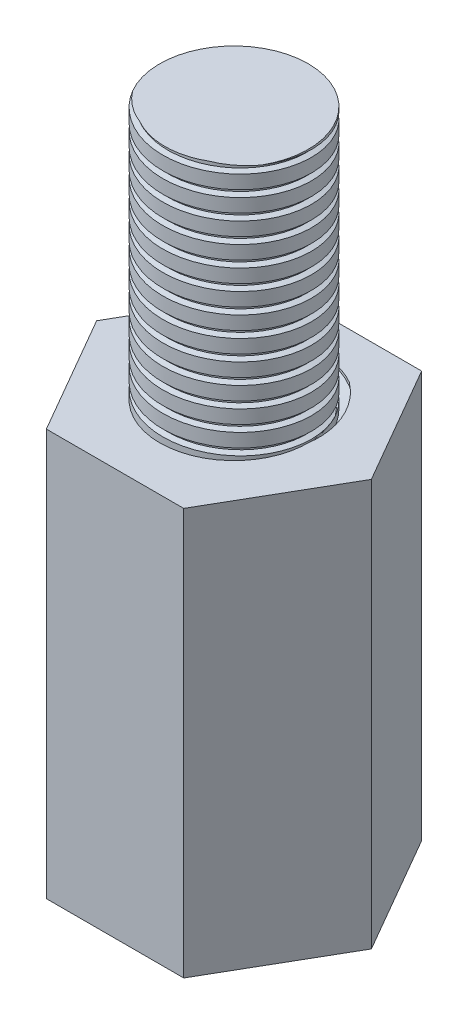
SolidWorks part; units mm, degrees
note: The reader was unsure of these and kept them because the rebuilt part matched: shared geometry of "草图1<3>".
ref_plane "前视基准面" through (0, 0, 0) normal (0, 0, 1) x (1, 0, 0)
ref_plane "上视基准面" through (0, 0, 0) normal (0, 1, 0) x (1, 0, 0)
ref_plane "右视基准面" through (0, 0, 0) normal (1, 0, 0) x (0, 0, -1)
sketch "草图1" plane through (0, 0, 0) normal (0, 1, 0) x (1, 0, 0)
  line L0 (0, 0) -> (0, 4.5761) construction
  line L1 (1.351, -2.34) -> (2.702, 0)
  line L2 (2.702, 0) -> (1.351, 2.34)
  line L3 (1.351, 2.34) -> (-1.351, 2.34)
  line L4 (-1.351, 2.34) -> (-2.702, 0)
  line L5 (-2.702, 0) -> (-1.351, -2.34)
  line L6 (-1.351, -2.34) -> (1.351, -2.34)
  line L7 (0, 4.5761) -> (0, -3.6794) construction
  circle A0 centre (0, 0) radius 2.34 construction
  circle A1 centre (0, 0) radius 1.46
  dimension "D1" = 4.68
  dimension "D2" = 2.92
extrude "凸台-拉伸1" add sketch "草图1" along normal blind 8 contours A1 | L5 L6 L1 L2 L3 L4 A1
extrude "切除-拉伸1" cut sketch "草图1<3>" along normal blind 5 contours A1
sketch "草图1<3>" plane through (0, 0, 0) normal (0, 1, 0) x (1, 0, 0) same geometry as "草图1"
sketch "草图2" plane through (0, 8, 0) normal (0, 1, 0) x (1, 0, 0)
  circle A0 centre (0, 0) radius 1.46
  dimension "D1" = 2.92
extrude "凸台-拉伸2" add sketch "草图2" along normal blind 5 separate body
ref_plane "基准面1" through (0, 0, 0) normal (0, 0, -1) x (-1, 0, 0)
sketch "草图4" plane through (0, 0, 0) normal (0, 0, -1) x (-1, 0, 0)
  line L0 (0, 0) -> (0, 28.5702) construction
  line L1 (-1.56, 8) -> (-1.56, 8.2)
  line L2 (-1.56, 8.2) -> (-1.36, 8.1333)
  line L3 (-1.36, 8.0667) -> (-1.56, 8)
  line L4 (-1.26, 8.1) -> (-2.0659, 8.1) construction
  line L5 (-2.0659, 8.1) -> (-0.8933, 8.1) construction
  line L7 (-1.46, 13) -> (-1.46, 8) construction
  line L8 (-1.36, 8.1333) -> (-1.36, 8.0667)
  line L9 (-1.46, 8) -> (1.46, 8) construction
  point P14 (0, 0)
  point P15 (0, 0)
  dimension "D1" = 0.1
  dimension "D2" = 0.1
  dimension "D3" = 0.1
  dimension "D4" = 0.3
  dimension "D5" = 0.2
  dimension "D6" = 0.1
  dimension "D7" = 0.0667
  dimension "D8" = 0.0667
ref_plane "基准面2" through (0, 8.1, 0) normal (0, 1, 0) x (1, 0, 0)
sketch "草图5" plane through (0, 8.1, 0) normal (0, 1, 0) x (1, 0, 0)
  circle A0 centre (0, 0) radius 1.46
  dimension "D1" = 2.92
curve "螺旋线/涡状线1" pitch 0.4 height 7.5 turns 18.75
sweep "切除-扫描1" cut profiles "草图4" path "螺旋线/涡状线1"
sketch "草图6" plane through (0, 0, 0) normal (0, -1, 0) x (1, 0, 0)
  circle A0 centre (0, 0) radius 1.46
curve "螺旋线/涡状线2" pitch 0.4 height 9.5 turns 23.75
sketch "草图7" plane through (0, 0, 0) normal (0, 0, -1) x (-1, 0, 0)
  line L0 (1.46, 0.2) -> (1.66, 0.1333)
  line L1 (1.66, 0.0667) -> (1.46, 0)
  line L2 (1.46, 0.2) -> (1.46, 0)
  line L3 (1.66, 0.1333) -> (1.66, 0.0667)
  line L8 (1.351, 0) -> (-1.351, 0) construction
  dimension "D1" = 0.2
  dimension "D3" = 1.46
  dimension "D4" = 0.2
sweep "切除-扫描2" cut profiles "草图7" path "螺旋线/涡状线2"
equation "\"chang\"= 20mm"
equation "\"r\"= 2.92mm"
equation "\"luowengao\"= 6.5mm"
equation "\"rr\"= 4.68mm"
equation "\"D1@草图1\"=\"rr\""
equation "\"D2@草图1\"=\"r\""
equation "\"D1@凸台-拉伸1\"=\"chang\""
equation "\"D1@切除-拉伸1\"=\"luowengao\"+5mm"
equation "\"D1@草图2\"=\"r\""
equation "\"D1@凸台-拉伸2\"=\"luowengao\""
